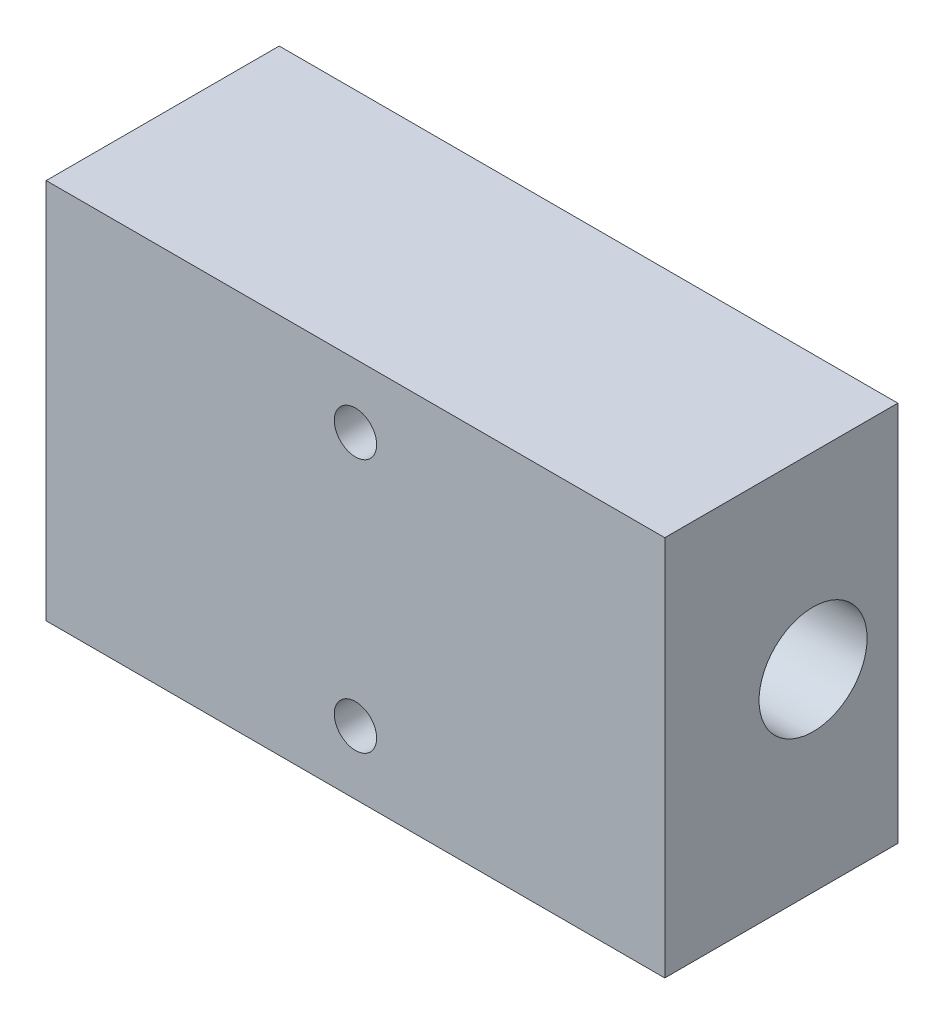
SolidWorks part; units mm, degrees
ref_plane "Alzado" through (0, 0, 0) normal (0, 0, 1) x (1, 0, 0)
ref_plane "Planta" through (0, 0, 0) normal (0, 1, 0) x (1, 0, 0)
ref_plane "Vista lateral" through (0, 0, 0) normal (1, 0, 0) x (0, 0, -1)
sketch "Croquis1" plane through (0, 0, 0) normal (0, 0, 1) x (1, 0, 0)
  line L1 (0, 0) -> (58.4, 0)
  line L2 (0, 0) -> (0, 36)
  line L3 (0, 36) -> (58.4, 36)
  line L4 (58.4, 0) -> (58.4, 36)
  dimension "D1" = 36
  dimension "D2" = 58.4
extrude "Saliente-Extruir1" add sketch "Croquis1" along normal blind 22
sketch "Croquis2" plane through (58.4, 0, 0) normal (1, 0, 0) x (0, 0, -1)
  circle A0 centre (-8, 18.2363) radius 5.1
  dimension "D1" = 10.2
  dimension "D2" = 8
extrude "Cortar-Extruir1" cut sketch "Croquis2" against normal through all
hole_wizard "Taladros de espiga de Ø4.0mm2" positions "Croquis4" profile "Croquis5" hole size "Ø4.0" standard "DIN"
sketch "Croquis4" plane through (0, 0, 22) normal (0, 0, 1) x (1, 0, 0)
  line L0 (0, 30) -> (58.4, 30) construction
  line L1 (0, 36) -> (0, 0) construction
  line L2 (58.4, 0) -> (58.4, 36) construction
  line L5 (58.4, 6) -> (0, 6) construction
  line L7 (58.4, 36) -> (0, 36) construction
  line L8 (29.2, 36) -> (29.2, 0) construction
  line L9 (0, 0) -> (58.4, 0) construction
  point P24 (29.2, 30)
  point P26 (29.2, 6)
  dimension "D1" = 6
  dimension "D2" = 6
sketch "Croquis5" plane through (29.2, 6, 22) normal (1, 0, 0) x (0, -1, 0)
  line L0 (0, 0) -> (0, 13.2017)
  line L1 (0, 13.2017) -> (2, 12)
  line L2 (2, 12) -> (2, 0)
  line L5 (2, 0) -> (0, 0)
  line L10 (0, 13.2017) -> (-2, 12) construction
  line L11 (0, -6.35) -> (0, 107.95) construction
  dimension "Diámetro de taladro" = 4
  dimension "Profundidad de taladro" = 12
  dimension "Ángulo de perforador" = 118
